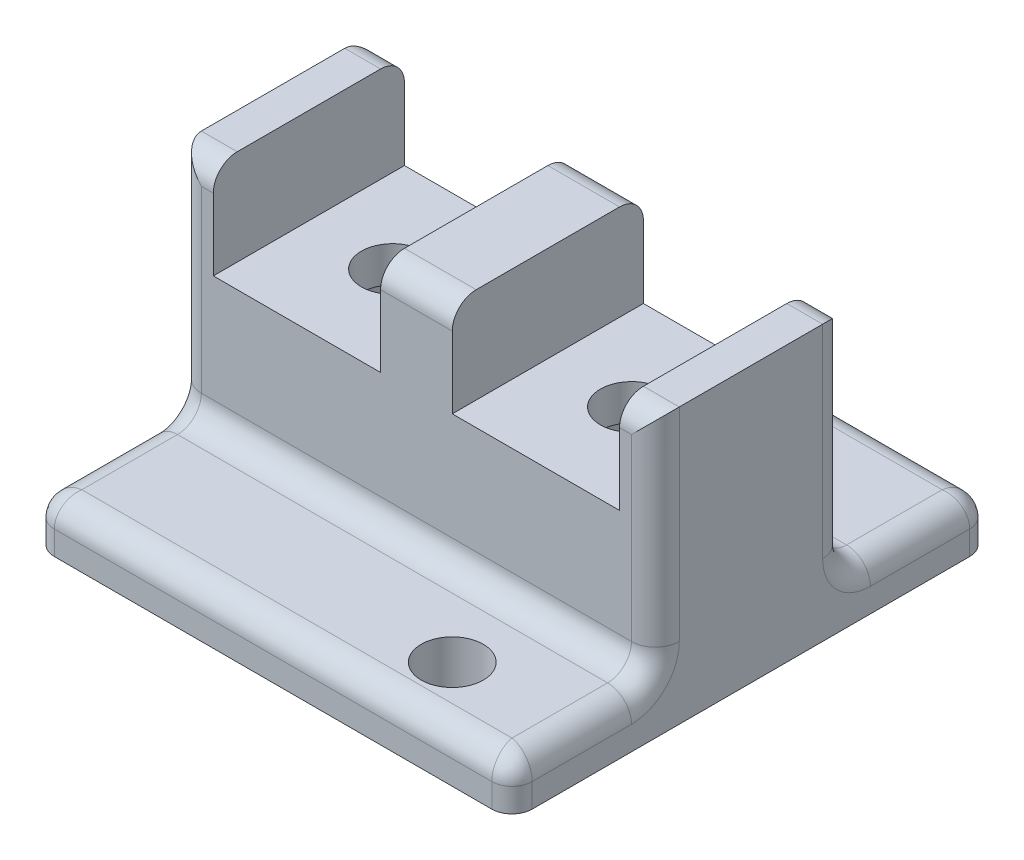
SolidWorks part; units mm, degrees
ref_plane "Front Plane" through (0, 0, 0) normal (0, 0, 1) x (1, 0, 0)
ref_plane "Top Plane" through (0, 0, 0) normal (0, 1, 0) x (1, 0, 0)
ref_plane "Right Plane" through (0, 0, 0) normal (1, 0, 0) x (0, 0, -1)
sketch "Sketch1" plane through (0, 0, 0) normal (0, 1, 0) x (1, 0, 0)
  line L1 (1.692, 0) -> (38.308, 0)
  line L2 (0, 1.692) -> (0, 38.308)
  line L3 (1.692, 40) -> (38.308, 40)
  line L4 (40, 1.692) -> (40, 38.308)
  arc A0 (1.692, 40) -> (0, 38.308) centre (1.692, 38.308) ccw
  arc A1 (1.692, 0) -> (0, 1.692) centre (1.692, 1.692) cw
  arc A2 (40, 1.692) -> (38.308, 0) centre (38.308, 1.692) cw
  arc A3 (40, 38.308) -> (38.308, 40) centre (38.308, 38.308) ccw
  point P7 (0, 40)
  point P10 (0, 0)
  point P13 (40, 0)
  dimension "D3" = 1.692
  dimension "D4" = 1.692
  dimension "D1" = 40
  dimension "D2" = 40
extrude "Boss-Extrude1" add sketch "Sketch1" along normal blind 15
sketch "Sketch2" plane through (0, 15, 0) normal (0, 1, 0) x (1, 0, 0)
  line L0 (0, 38.308) -> (0, 1.692) construction
  line L1 (0, 28) -> (40, 28)
  line L2 (0, 28) -> (0, 40)
  line L3 (0, 40) -> (40, 40)
  line L4 (40, 28) -> (40, 40)
  line L5 (40, 1.692) -> (40, 38.308) construction
  line L6 (0, 12) -> (40, 12)
  line L7 (0, 12) -> (0, 0)
  line L8 (0, 0) -> (40, 0)
  line L9 (40, 12) -> (40, 0)
  line L10 (20, 28) -> (20, 12) construction
  line L11 (38.308, 40) -> (1.692, 40) construction
  line L12 (1.692, 0) -> (38.308, 0) construction
  point P14 (20, 20)
  point P15 (40, 20)
  dimension "D1" = 16
  dimension "D2" = 12
extrude "Cut-Extrude1" cut sketch "Sketch2" against normal offset from surface (11 mm away) 4 up to face at (20, 0, -20)
sketch "Sketch3" plane through (0, 4, 0) normal (0, 1, 0) x (1, 0, 0)
  line L0 (1.692, 40) -> (38.308, 40) construction
  line L1 (10, 35) -> (30, 35) construction
  line L2 (10, 35) -> (10, 5) construction
  line L3 (10, 5) -> (30, 5) construction
  line L4 (30, 35) -> (30, 5) construction
  line L5 (0, 28) -> (0, 12) construction
  line L6 (0, 28) -> (0, 38.308) construction
  circle A0 centre (10, 35) radius 2.6
  circle A1 centre (30, 5) radius 2.6
  point P4 (20, 35)
  point P7 (20, 40)
  point P10 (0, 20)
  point P11 (10, 20)
  dimension "D3" = 5.2
  dimension "D1" = 5
  dimension "D2" = 10
extrude "Cut-Extrude2" cut sketch "Sketch3" against normal blind 4
sketch "Sketch4" plane through (0, 15, 0) normal (0, 1, 0) x (1, 0, 0)
  line L0 (10, 20) -> (30, 20) construction
  line L1 (0, 28) -> (0, 12) construction
  line L2 (0, 28) -> (40, 28) construction
  circle A0 centre (10, 20) radius 2.6
  circle A1 centre (30, 20) radius 2.6
  point P4 (0, 20)
  point P7 (20, 28)
  point P8 (20, 20)
  dimension "D2" = 5.2
  dimension "D1" = 10
extrude "Cut-Extrude3" cut sketch "Sketch4" against normal through all
sketch "Sketch5" plane through (0, 15, 0) normal (0, 1, 0) x (1, 0, 0)
  line L0 (40, 12) -> (0, 12) construction
  line L1 (0, 28) -> (3, 28)
  line L2 (0, 28) -> (0, 12)
  line L3 (0, 12) -> (3, 12)
  line L4 (3, 28) -> (3, 12)
  line L5 (0, 28) -> (40, 28) construction
  line L6 (17, 28) -> (23, 28)
  line L7 (17, 28) -> (17, 12)
  line L8 (17, 12) -> (23, 12)
  line L9 (23, 28) -> (23, 12)
  line L10 (0, 12) -> (40, 12) construction
  line L12 (40, 28) -> (37, 28)
  line L13 (40, 28) -> (40, 12)
  line L14 (40, 12) -> (37, 12)
  line L15 (37, 28) -> (37, 12)
  circle A0 centre (30, 20) radius 2.6 construction
  point P20 (20, 28)
  point P21 (20, 28)
  dimension "D3" = 7
  dimension "D1" = 3
  dimension "D2" = 6
  dimension "D4" = 7
extrude "Boss-Extrude2" add sketch "Sketch5" along normal blind 8
sketch "Sketch6" plane through (0, 0, 0) normal (0, -1, 0) x (1, 0, 0)
  line L1 (27.6329, -15.9) -> (25.2657, -20)
  line L2 (25.2657, -20) -> (27.6329, -24.1)
  line L3 (27.6329, -24.1) -> (32.3671, -24.1)
  line L4 (32.3671, -24.1) -> (34.7343, -20)
  line L5 (34.7343, -20) -> (32.3671, -15.9)
  line L6 (32.3671, -15.9) -> (27.6329, -15.9)
  line L7 (7.6329, -15.9) -> (5.2657, -20)
  line L8 (5.2657, -20) -> (7.6329, -24.1)
  line L9 (7.6329, -24.1) -> (12.3671, -24.1)
  line L10 (12.3671, -24.1) -> (14.7343, -20)
  line L11 (14.7343, -20) -> (12.3671, -15.9)
  line L12 (12.3671, -15.9) -> (7.6329, -15.9)
  circle A0 centre (30, -20) radius 4.1 construction
  circle A1 centre (10, -20) radius 4.1 construction
  dimension "D1" = 8.2
extrude "Cut-Extrude4" cut sketch "Sketch6" against normal offset from surface (12 mm away) 3 up to face at (10, 15, -17.4)
fillet "Fillet1" radius 2 2 edges at (20, 4, -28) (20, 4, -12)
fillet "Fillet2" radius 2 24 edges at (0, 14.5, -28) (0, 4, -34.154) (0.4956, 4, -39.5044) (20, 4, -40) (39.5044, 4, -39.5044) (40, 4, -34.154) (40, 14.5, -28) (0, 14.5, -12) (0, 4.5858, -11.4142) (0, 4, -5.846) (0.4956, 4, -0.4956) (20, 4, 0) (39.5044, 4, -0.4956) (40, 4, -5.846) (40, 4.5858, -11.4142) (0, 4.5858, -28.5858) (40, 4.5858, -28.5858) (40, 14.5, -12) (1.5, 23, -12) (20, 23, -12) (38.5, 23, -28) (38.5, 23, -12) (20, 23, -28) (1.5, 23, -28)
